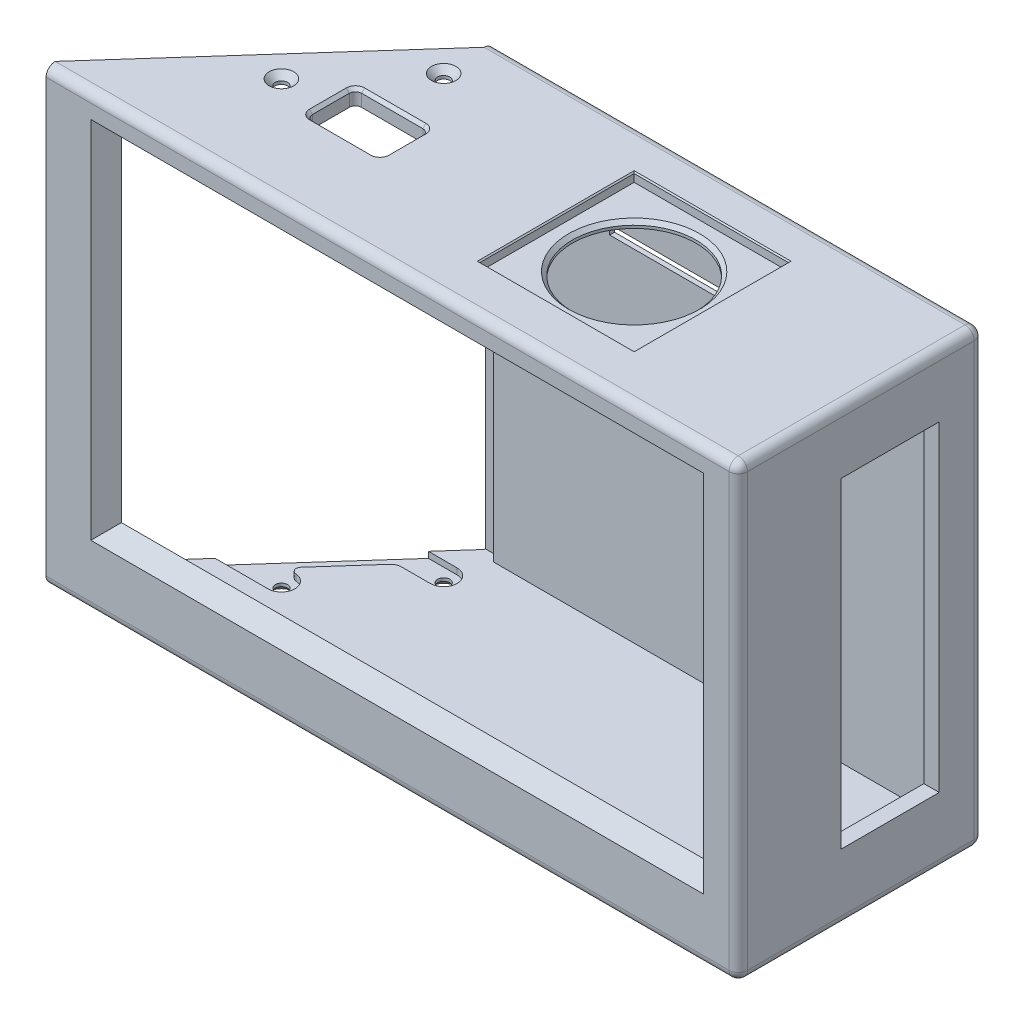
SolidWorks part; units mm, degrees
ref_plane "Plan de face" through (0, 0, 0) normal (0, 0, 1) x (1, 0, 0)
ref_plane "Plan de dessus" through (0, 0, 0) normal (0, 1, 0) x (1, 0, 0)
ref_plane "Plan de droite" through (0, 0, 0) normal (1, 0, 0) x (0, 0, -1)
sketch "Esquisse2" plane through (0, 0, 0) normal (0, 1, 0) x (1, 0, 0)
  line L0 (0, 0) -> (113, 0)
  line L5 (113, 0) -> (113, 40)
  line L6 (113, 40) -> (33, 40)
  line L8 (33, 40) -> (33, 38.7)
  line L11 (35.5, 37.5) -> (110.5, 37.5)
  line L12 (110.5, 37.5) -> (110.5, 2.5)
  line L13 (110.5, 2.5) -> (2.5, 2.5)
  line L14 (2.5, 2.5) -> (2.5, 1.3)
  line L15 (2.5, 1.3) -> (0, 1.3)
  line L16 (0, 1.3) -> (0, 0)
  line L17 (33, 38.7) -> (35.5, 38.7)
  line L18 (35.5, 38.7) -> (35.5, 37.5)
  dimension "D1" = 40
  dimension "D2" = 35
  dimension "D3" = 2.5
  dimension "D4" = 2.5
  dimension "D5" = 1.3
  dimension "D6" = 2.5
  dimension "D7" = 113
  dimension "D8" = 108
  dimension "D9" = 80
  dimension "D10" = 75
  dimension "D11" = 2.5
  dimension "D12" = 1.2
  dimension "D13" = 1.3
extrude "Boss.-Extru.1" add sketch "Esquisse2" along normal blind 68.5
sketch "Esquisse3" plane through (0, 0, 0) normal (0, -1, 0) x (1, 0, 0)
  line L0 (0, 0) -> (113, 0)
  line L1 (113, 0) -> (113, -40)
  line L2 (113, -40) -> (33, -40)
  line L3 (33, -40) -> (33, -38.5)
  line L4 (33, -38.5) -> (0, -1.5)
  line L5 (0, -1.5) -> (0, 0)
  dimension "D1" = 1.5
  dimension "D2" = 1.5
extrude "Boss.-Extru.2" add sketch "Esquisse3" along normal blind 2.5
sketch "Esquisse4" plane through (0, 0, 0) normal (0, 0, 1) x (1, 0, 0)
  line L0 (113, 68.5) -> (113, -2.5) construction
  line L1 (9.8, 64.7) -> (104.8, 64.7)
  line L2 (9.8, 64.7) -> (9.8, 10.2)
  line L3 (9.8, 10.2) -> (104.8, 10.2)
  line L4 (104.8, 64.7) -> (104.8, 10.2)
  line L5 (113, -2.5) -> (0, -2.5) construction
  line L6 (0, 68.5) -> (113, 68.5) construction
  dimension "D1" = 8.2
  dimension "D2" = 12.7
  dimension "D3" = 54.5
  dimension "D4" = 95
  dimension "D5" = 3.8
extrude "Enlèv. mat.-Extru.1" cut sketch "Esquisse4" against normal blind 2.5
sketch "Esquisse5" plane through (113, 0, 0) normal (1, 0, 0) x (0, 0, -1)
  line L0 (0, 68.5) -> (0, -2.5) construction
  line L1 (16.8, 60.9) -> (32.8, 60.9)
  line L2 (16.8, 60.9) -> (16.8, 8.5)
  line L3 (16.8, 8.5) -> (32.8, 8.5)
  line L4 (32.8, 60.9) -> (32.8, 8.5)
  line L5 (40, -2.5) -> (0, -2.5) construction
  line L6 (40, 68.5) -> (40, -2.5) construction
  dimension "D1" = 16.8
  dimension "D2" = 16
  dimension "D3" = 52.4
  dimension "D4" = 11
  dimension "D5" = 7.2
extrude "Enlèv. mat.-Extru.2" cut sketch "Esquisse5" against normal blind 2.5
sketch "Esquisse6" plane through (0, 68.5, 0) normal (0, 1, 0) x (1, 0, 0)
  line L0 (33, 40) -> (33, 38.5)
  line L1 (33, 38.5) -> (0, 1.5)
  line L2 (0, 1.5) -> (0, 0)
  line L3 (0, 0) -> (113, 0)
  line L4 (113, 0) -> (113, 40)
  line L5 (113, 40) -> (33, 40)
extrude "Boss.-Extru.3" add sketch "Esquisse6" along normal blind 2.5
chamfer "Chanfrein1" distance 2.5 angle 45 4 edges at (57.3, 10.2, 0) (104.8, 37.45, 0) (57.3, 64.7, 0) (9.8, 37.45, 0)
fillet "Congé1" radius 1.5 8 edges at (73, -2.5, -40) (113, -2.5, -20) (113, 34.25, -40) (56.5, -2.5, 0) (113, 34.25, 0) (73, 71, -40) (113, 71, -20) (56.5, 71, 0)
sketch "Esquisse7" plane through (0, 0, -40) normal (0, 0, -1) x (-1, 0, 0)
  line L0 (-113, -1) -> (-113, 69.5) construction
  line L1 (-86.45, 56.7) -> (-42.55, 56.7)
  line L2 (-86.45, 56.7) -> (-86.45, 13.2)
  line L4 (-42.55, 56.7) -> (-42.55, 13.2)
  line L5 (-111.5, 71) -> (-33, 71) construction
  line L6 (-39.8, 10.3) -> (-89.2, 10.3)
  line L7 (-89.2, 10.3) -> (-89.2, 13.2)
  line L8 (-89.2, 13.2) -> (-86.45, 13.2)
  line L9 (-39.8, 13.2) -> (-39.8, 10.3)
  line L10 (-42.55, 13.2) -> (-39.8, 13.2)
  dimension "D1" = 26.55
  dimension "D2" = 43.9
  dimension "D4" = 14.3
  dimension "D5" = 49.4
  dimension "D6" = 2.75
  dimension "D8" = 2.9
  dimension "D9" = 46.4
extrude "Enlèv. mat.-Extru.3" cut sketch "Esquisse7" against normal blind 1.2
chamfer "Chanfrein2" distance 0.3 angle 45 8 edges at (86.45, 34.95, -40) (64.5, 56.7, -40) (42.55, 34.95, -40) (39.8, 11.75, -40) (41.175, 13.2, -40) (64.5, 10.3, -40) (89.2, 11.75, -40) (87.825, 13.2, -40)
sketch "Esquisse8" plane through (0, 0, -38.8) normal (0, 0, -1) x (-1, 0, 0)
  line L6 (-42.55, 56.7) -> (-86.45, 56.7) construction
  line L7 (-74.5, 56.7) -> (-54.5, 56.7)
  line L8 (-74.5, 56.7) -> (-74.5, 55.7)
  line L9 (-74.5, 55.7) -> (-54.5, 55.7)
  line L10 (-54.5, 56.7) -> (-54.5, 55.7)
  line L11 (-86.45, 56.7) -> (-86.45, 13.2) construction
  line L12 (-42.55, 13.2) -> (-42.55, 56.7) construction
  dimension "D1" = 1
  dimension "D2" = 20
  dimension "D3" = 11.95
  dimension "D4" = 11.95
extrude "Enlèv. mat.-Extru.4" cut sketch "Esquisse8" against normal blind 3
chamfer "Chanfrein3" distance 0.5 angle 45 3 edges at (54.5, 56.2, -38.8) (74.5, 56.2, -38.8) (64.5, 55.7, -38.8)
chamfer "Chanfrein4" distance 0.5 angle 45 1 edges at (64.5, 56.7, -37.5)
sketch "Esquisse9" plane through (0, 71, 0) normal (0, 1, 0) x (1, 0, 0)
  line L0 (110.5, 2.5) -> (2.5, 2.5) construction
  line L3 (20.9203, 17.5) -> (14.2703, 17.5) construction
  line L4 (33, 38.5) -> (0, 1.5) construction
  line L5 (20.9203, 17.5) -> (33.4068, 31.5) construction
  circle A0 centre (20.9203, 17.5) radius 1
  circle A1 centre (33.4068, 31.5) radius 1
  dimension "D1" = 2
  dimension "D4" = 2
  dimension "D2" = 15
  dimension "D3" = 6.65
  dimension "D5" = 14
extrude "Enlèv. mat.-Extru.5" cut sketch "Esquisse9" against normal blind 75
chamfer "Chanfrein5" distance 1 angle 45 2 edges at (20.9203, 71, -16.5) (33.4068, 71, -30.5)
chamfer "Chanfrein6" distance 1 angle 45 2 edges at (20.9203, -2.5, -16.5) (33.4068, -2.5, -30.5)
sketch "Esquisse10" plane through (0, 0, 0) normal (0, 1, 0) x (1, 0, 0)
  line L4 (21.0501, 19.4967) -> (21.1093, 19.491)
  line L9 (12.0401, 15.2999) -> (28.4509, 33.7)
  line L10 (28.4509, 33.7) -> (33.4067, 33.7)
  line L11 (33.4064, 29.3) -> (28.7356, 29.3007)
  line L12 (20.5476, 21.0247) -> (27.392, 28.6988)
  line L13 (21.069, 19.6958) -> (21.1282, 19.6902)
  line L14 (12.0401, 15.2999) -> (20.9203, 15.3)
  line L15 (28.5405, 33.5) -> (33.4067, 33.5) construction
  line L16 (33.4065, 29.5) -> (28.7356, 29.5007) construction
  line L17 (20.3983, 21.1578) -> (27.2428, 28.8319) construction
  line L18 (12.4864, 15.4999) -> (20.9203, 15.5) construction
  line L19 (12.4864, 15.4999) -> (28.5405, 33.5) construction
  line L20 (0, 1.5) -> (111.5, 1.5) construction
  arc A4 (33.4064, 29.3) -> (33.4067, 33.7) centre (33.4068, 31.5) ccw
  arc A5 (28.7356, 29.3007) -> (27.392, 28.6988) centre (28.7354, 27.5007) ccw
  arc A6 (20.5476, 21.0247) -> (21.069, 19.6958) centre (21.1446, 20.4922) ccw
  arc A7 (20.9203, 15.3) -> (21.1282, 19.6902) centre (20.9203, 17.5) ccw
  arc A8 (33.4065, 29.5) -> (33.4067, 33.5) centre (33.4068, 31.5) ccw construction
  arc A9 (28.7356, 29.5007) -> (27.2428, 28.8319) centre (28.7354, 27.5007) ccw construction
  arc A10 (20.3983, 21.1578) -> (21.0501, 19.4967) centre (21.1446, 20.4922) ccw construction
  arc A11 (20.9203, 15.5) -> (21.1093, 19.491) centre (20.9203, 17.5) ccw construction
  dimension "D1" = 2.2
  dimension "D2" = 2.2
  dimension "D3" = 8.8802
  dimension "D4" = 18.4
  dimension "D9" = 1.8
  dimension "D12" = 0.8
  dimension "D6" = 16.4108
  dimension "D7" = 4.9558
  dimension "D8" = 4.6708
  dimension "D10" = 10.2829
  dimension "D11" = 6.8445
  dimension "D13" = 13.7999
  dimension "D14" = 12.0401
  dimension "D5" = 0.2
extrude "Enlèv. mat.-Extru.6" cut sketch "Esquisse10" against normal blind 1 contours L11 A5 L12 A6 L13 A7 L14 L9 L10 A4
sketch "Esquisse12" plane through (0, 68.5, 0) normal (0, -1, 0) x (1, 0, 0)
  line L0 (12.3081, -15.3) -> (20.9203, -15.3)
  line L1 (21.0322, -19.7077) -> (21.2456, -19.6758)
  line L2 (20.5535, -21.0314) -> (27.3923, -28.6988)
  line L3 (28.7359, -29.3007) -> (33.4064, -29.3)
  line L4 (33.4067, -33.7) -> (28.7189, -33.7)
  line L5 (12.3081, -15.3) -> (28.7189, -33.7)
  line L7 (33.4067, -33.5) -> (27.9285, -33.5) construction
  arc A0 (21.2456, -19.6758) -> (20.9203, -15.3) centre (20.9203, -17.5) ccw
  arc A1 (33.4067, -33.7) -> (33.4064, -29.3) centre (33.4068, -31.5) ccw
  arc A2 (21.0322, -19.7077) -> (20.5535, -21.0314) centre (21.1506, -20.4989) ccw
  arc A3 (27.3923, -28.6988) -> (28.7359, -29.3007) centre (28.7356, -27.5007) ccw
  dimension "D1" = 4.4
  dimension "D2" = 1.6
  dimension "D3" = 3.6
  dimension "D4" = 4.4
  dimension "D5" = 10.9993
  dimension "D6" = 18.0011
  dimension "D7" = 18.4
  dimension "D8" = 16.4108
extrude "Enlèv. mat.-Extru.7" cut sketch "Esquisse12" against normal blind 1
sketch "Esquisse13" plane through (0, 71, 0) normal (0, 1, 0) x (1, 0, 0)
  line L0 (9.8, 2.5) -> (104.8, 2.5) construction
  line L1 (28, 22.5) -> (40, 22.5)
  line L2 (28, 22.5) -> (28, 14.5)
  line L3 (28, 14.5) -> (40, 14.5)
  line L4 (40, 22.5) -> (40, 14.5)
  line L6 (110.5, 16.8) -> (110.5, 32.8) construction
  dimension "D1" = 8
  dimension "D2" = 12
  dimension "D3" = 20
  dimension "D4" = 82.5
extrude "Enlèv. mat.-Extru.8" cut sketch "Esquisse13" against normal blind 2.5
fillet "Congé2" radius 1 4 edges at (28, 69.75, -22.5) (40, 69.75, -22.5) (40, 69.75, -14.5) (28, 69.75, -14.5)
chamfer "Chanfrein7" distance 0.5 angle 45 8 edges at (39.7071, 71, -14.7929) (40, 71, -18.5) (39.7071, 71, -22.2071) (34, 71, -22.5) (28.2929, 71, -22.2071) (28, 71, -18.5) (28.2929, 71, -14.7929) (34, 71, -14.5)
sketch "Esquisse14" plane through (0, 71, 0) normal (0, 1, 0) x (1, 0, 0)
  line L1 (62.9, 33.1) -> (88.1, 33.1)
  line L2 (62.9, 33.1) -> (62.9, 7.9)
  line L3 (62.9, 7.9) -> (88.1, 7.9)
  line L4 (88.1, 33.1) -> (88.1, 7.9)
  line L5 (113, 38.5) -> (113, 1.5) construction
  line L6 (111.5, 0) -> (0, 0) construction
  dimension "D1" = 25.2
  dimension "D2" = 25.2
  dimension "D3" = 50.1
  dimension "D4" = 33.1
extrude "Enlèv. mat.-Extru.9" cut sketch "Esquisse14" against normal blind 1.45
chamfer "Chanfrein8" distance 0.2 angle 45 4 edges at (75.5, 71, -7.9) (62.9, 71, -20.5) (75.5, 71, -33.1) (88.1, 71, -20.5)
sketch "Esquisse15" plane through (0, 69.55, 0) normal (0, 1, 0) x (1, 0, 0)
  circle A0 centre (75.5, 20.5) radius 10.1
  dimension "D1" = 20.2
extrude "Enlèv. mat.-Extru.10" cut sketch "Esquisse15" against normal blind 1.05
chamfer "Chanfrein9" distance 0.6 angle 45 1 edges at (75.5, 69.55, -10.4)
